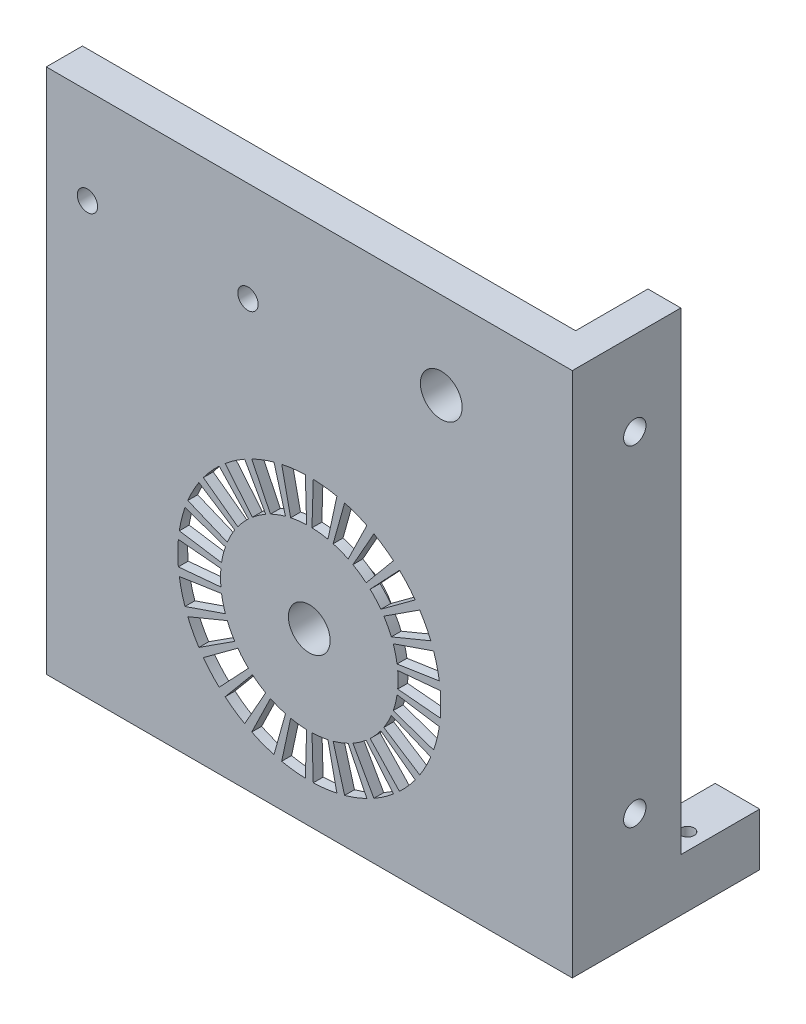
SolidWorks part; units mm, degrees
ref_plane "Front Plane" through (0, 0, 0) normal (0, 0, 1) x (1, 0, 0)
ref_plane "Top Plane" through (0, 0, 0) normal (0, 1, 0) x (1, 0, 0)
ref_plane "Right Plane" through (0, 0, 0) normal (1, 0, 0) x (0, 0, -1)
sketch "LED panel" plane through (0, 0, 0) normal (0, 0, 1) x (1, 0, 0)
  line L1 (-40, 40) -> (40, 40)
  line L2 (-40, 40) -> (-40, -40)
  line L3 (-40, -40) -> (40, -40)
  line L4 (40, 40) -> (40, -40)
  line L5 (-40, 40) -> (40, -40) construction
  line L6 (-40, -40) -> (40, 40) construction
  point P0 (0, 0)
  dimension "D1" = 80
  dimension "D2" = 80
extrude "Extrude LED panel" add sketch "LED panel" along normal blind 2.5
sketch "Sketch3" plane through (0, 0, 2.5) normal (0, 0, 1) x (1, 0, 0)
  circle A0 centre (0, -14) radius 5.9987
  circle A1 centre (20.0721, 26.7806) radius 6.0029
extrude "Boss-Extrude2" add sketch "Sketch3" against normal blind 7
sketch "Sketch1" plane through (0, 0, 2.5) normal (0, 0, 1) x (1, 0, 0)
  line L0 (-40, -14) -> (40, -14) construction
  line L3 (0, 40) -> (0, -40) construction
  line L4 (40, 40) -> (-40, 40) construction
  line L5 (-40, -40) -> (40, -40) construction
  line L6 (0, -14) -> (52.2337, -7.6577) construction
  line L7 (0, -14) -> (47.0949, -19.7184) construction
  line L8 (0, -14) -> (19.9179, -12.19) construction
  line L9 (0, -14) -> (41.9979, -17.8164) construction
  line L10 (13.4446, -12.7783) -> (19.9179, -12.19)
  line L11 (13.4446, -15.2217) -> (19.9179, -15.81)
  line L12 (13.3463, -16.0313) -> (19.7723, -17.0093)
  line L13 (12.7615, -18.4037) -> (18.906, -20.5241)
  line L14 (12.4724, -19.1662) -> (18.4776, -21.6537)
  line L15 (11.3368, -21.3298) -> (16.7953, -24.859)
  line L16 (10.8736, -22.0009) -> (16.109, -25.8532)
  line L17 (9.2533, -23.8299) -> (13.7085, -28.5628)
  line L18 (8.6429, -24.3707) -> (12.8043, -29.364)
  line L19 (6.6319, -25.7587) -> (9.8251, -31.4203)
  line L20 (5.9099, -26.1377) -> (8.7554, -31.9818)
  line L21 (3.6252, -27.0042) -> (5.3706, -33.2654)
  line L22 (2.8334, -27.1993) -> (4.1976, -33.5545)
  line L23 (0.4077, -27.4938) -> (0.6041, -33.9909)
  line L24 (-0.4077, -27.4938) -> (-0.6041, -33.9909)
  line L25 (-2.8334, -27.1993) -> (-4.1976, -33.5545)
  line L26 (-3.6252, -27.0042) -> (-5.3706, -33.2654)
  line L27 (-5.9099, -26.1377) -> (-8.7554, -31.9818)
  line L28 (-6.6319, -25.7587) -> (-9.8251, -31.4203)
  line L29 (-8.6429, -24.3707) -> (-12.8043, -29.364)
  line L30 (-9.2533, -23.8299) -> (-13.7085, -28.5628)
  line L31 (-10.8736, -22.0009) -> (-16.109, -25.8532)
  line L32 (-11.3368, -21.3298) -> (-16.7953, -24.859)
  line L33 (-12.4724, -19.1662) -> (-18.4776, -21.6537)
  line L34 (-12.7615, -18.4037) -> (-18.906, -20.5241)
  line L35 (-13.3463, -16.0313) -> (-19.7723, -17.0093)
  line L36 (-13.4446, -15.2217) -> (-19.9179, -15.81)
  line L37 (-13.4446, -12.7783) -> (-19.9179, -12.19)
  line L38 (-13.3463, -11.9687) -> (-19.7723, -10.9907)
  line L39 (-12.7615, -9.5963) -> (-18.906, -7.4759)
  line L40 (-12.4724, -8.8338) -> (-18.4776, -6.3463)
  line L41 (-11.3368, -6.6702) -> (-16.7953, -3.141)
  line L42 (-10.8736, -5.9991) -> (-16.109, -2.1468)
  line L43 (-9.2533, -4.1701) -> (-13.7085, 0.5628)
  line L44 (-8.6429, -3.6293) -> (-12.8043, 1.364)
  line L45 (-6.6319, -2.2413) -> (-9.8251, 3.4203)
  line L46 (-5.9099, -1.8623) -> (-8.7554, 3.9818)
  line L47 (-3.6252, -0.9958) -> (-5.3706, 5.2654)
  line L48 (-2.8334, -0.8007) -> (-4.1976, 5.5545)
  line L49 (-0.4077, -0.5062) -> (-0.6041, 5.9909)
  line L50 (0.4077, -0.5062) -> (0.6041, 5.9909)
  line L51 (2.8334, -0.8007) -> (4.1976, 5.5545)
  line L52 (3.6252, -0.9958) -> (5.3706, 5.2654)
  line L53 (5.9099, -1.8623) -> (8.7554, 3.9818)
  line L54 (6.6319, -2.2413) -> (9.8251, 3.4203)
  line L55 (8.6429, -3.6293) -> (12.8043, 1.364)
  line L56 (9.2533, -4.1701) -> (13.7085, 0.5628)
  line L57 (10.8736, -5.9991) -> (16.109, -2.1468)
  line L58 (11.3368, -6.6702) -> (16.7953, -3.141)
  line L59 (12.4724, -8.8338) -> (18.4776, -6.3463)
  line L60 (12.7615, -9.5963) -> (18.906, -7.4759)
  line L61 (13.3463, -11.9687) -> (19.7723, -10.9907)
  line L62 (-40, -40) -> (40, -40) construction
  line L63 (40, -40) -> (40, 40) construction
  line L64 (-40, 40) -> (-40, -40) construction
  arc A0 (19.9179, -15.81) -> (19.9179, -12.19) centre (0, -14) ccw
  arc A1 (13.4446, -15.2217) -> (13.4446, -12.7783) centre (0, -14) ccw
  arc A2 (18.906, -20.5241) -> (19.7723, -17.0093) centre (0, -14) ccw
  arc A3 (12.7615, -18.4037) -> (13.3463, -16.0313) centre (0, -14) ccw
  arc A4 (16.7953, -24.859) -> (18.4776, -21.6537) centre (0, -14) ccw
  arc A5 (11.3368, -21.3298) -> (12.4724, -19.1662) centre (0, -14) ccw
  arc A6 (13.7085, -28.5628) -> (16.109, -25.8532) centre (0, -14) ccw
  arc A7 (9.2533, -23.8299) -> (10.8736, -22.0009) centre (0, -14) ccw
  arc A8 (9.8251, -31.4203) -> (12.8043, -29.364) centre (0, -14) ccw
  arc A9 (6.6319, -25.7587) -> (8.6429, -24.3707) centre (0, -14) ccw
  arc A10 (5.3706, -33.2654) -> (8.7554, -31.9818) centre (0, -14) ccw
  arc A11 (3.6252, -27.0042) -> (5.9099, -26.1377) centre (0, -14) ccw
  arc A12 (0.6041, -33.9909) -> (4.1976, -33.5545) centre (0, -14) ccw
  arc A13 (0.4077, -27.4938) -> (2.8334, -27.1993) centre (0, -14) ccw
  arc A14 (-4.1976, -33.5545) -> (-0.6041, -33.9909) centre (0, -14) ccw
  arc A15 (-2.8334, -27.1993) -> (-0.4077, -27.4938) centre (0, -14) ccw
  arc A16 (-8.7554, -31.9818) -> (-5.3706, -33.2654) centre (0, -14) ccw
  arc A17 (-5.9099, -26.1377) -> (-3.6252, -27.0042) centre (0, -14) ccw
  arc A18 (-12.8043, -29.364) -> (-9.8251, -31.4203) centre (0, -14) ccw
  arc A19 (-8.6429, -24.3707) -> (-6.6319, -25.7587) centre (0, -14) ccw
  arc A20 (-16.109, -25.8532) -> (-13.7085, -28.5628) centre (0, -14) ccw
  arc A21 (-10.8736, -22.0009) -> (-9.2533, -23.8299) centre (0, -14) ccw
  arc A22 (-18.4776, -21.6537) -> (-16.7953, -24.859) centre (0, -14) ccw
  arc A23 (-12.4724, -19.1662) -> (-11.3368, -21.3298) centre (0, -14) ccw
  arc A24 (-19.7723, -17.0093) -> (-18.906, -20.5241) centre (0, -14) ccw
  arc A25 (-13.3463, -16.0313) -> (-12.7615, -18.4037) centre (0, -14) ccw
  arc A26 (-19.9179, -12.19) -> (-19.9179, -15.81) centre (0, -14) ccw
  arc A27 (-13.4446, -12.7783) -> (-13.4446, -15.2217) centre (0, -14) ccw
  arc A28 (-18.906, -7.4759) -> (-19.7723, -10.9907) centre (0, -14) ccw
  arc A29 (-12.7615, -9.5963) -> (-13.3463, -11.9687) centre (0, -14) ccw
  arc A30 (-16.7953, -3.141) -> (-18.4776, -6.3463) centre (0, -14) ccw
  arc A31 (-11.3368, -6.6702) -> (-12.4724, -8.8338) centre (0, -14) ccw
  arc A32 (-13.7085, 0.5628) -> (-16.109, -2.1468) centre (0, -14) ccw
  arc A33 (-9.2533, -4.1701) -> (-10.8736, -5.9991) centre (0, -14) ccw
  arc A34 (-9.8251, 3.4203) -> (-12.8043, 1.364) centre (0, -14) ccw
  arc A35 (-6.6319, -2.2413) -> (-8.6429, -3.6293) centre (0, -14) ccw
  arc A36 (-5.3706, 5.2654) -> (-8.7554, 3.9818) centre (0, -14) ccw
  arc A37 (-3.6252, -0.9958) -> (-5.9099, -1.8623) centre (0, -14) ccw
  arc A38 (-0.6041, 5.9909) -> (-4.1976, 5.5545) centre (0, -14) ccw
  arc A39 (-0.4077, -0.5062) -> (-2.8334, -0.8007) centre (0, -14) ccw
  arc A40 (4.1976, 5.5545) -> (0.6041, 5.9909) centre (0, -14) ccw
  arc A41 (2.8334, -0.8007) -> (0.4077, -0.5062) centre (0, -14) ccw
  arc A42 (8.7554, 3.9818) -> (5.3706, 5.2654) centre (0, -14) ccw
  arc A43 (5.9099, -1.8623) -> (3.6252, -0.9958) centre (0, -14) ccw
  arc A44 (12.8043, 1.364) -> (9.8251, 3.4203) centre (0, -14) ccw
  arc A45 (8.6429, -3.6293) -> (6.6319, -2.2413) centre (0, -14) ccw
  arc A46 (16.109, -2.1468) -> (13.7085, 0.5628) centre (0, -14) ccw
  arc A47 (10.8736, -5.9991) -> (9.2533, -4.1701) centre (0, -14) ccw
  arc A48 (18.4776, -6.3463) -> (16.7953, -3.141) centre (0, -14) ccw
  arc A49 (12.4724, -8.8338) -> (11.3368, -6.6702) centre (0, -14) ccw
  arc A50 (19.7723, -10.9907) -> (18.906, -7.4759) centre (0, -14) ccw
  arc A51 (13.3463, -11.9687) -> (12.7615, -9.5963) centre (0, -14) ccw
  circle A52 centre (0, -14) radius 3.175
  point P124 (0, -14)
  dimension "D2" = 40
  dimension "D4" = 6.5
  dimension "D9" = 6.35
  dimension "D1" = 6.923
  dimension "D3" = 6.923
  dimension "D5" = 5.192
  dimension "D6" = 5.192
  dimension "D8" = 26
  dimension "D7" = 26
extrude "Cut arrow indication holes" cut sketch "Sketch1" against normal through all
sketch "Sketch4" plane through (0, 0, 0) normal (0, 0, 1) x (1, 0, 0)
  circle A0 centre (20.0721, 26.7806) radius 3.175
  dimension "D1" = 6.35
  dimension "D2" = 20.0721
  dimension "D3" = 26.7806
extrude "Cut hole for secondary rod" cut sketch "Sketch4" along normal through all and the other way blind 7
sketch "Sketch2" plane through (0, 0, 0) normal (0, 0, -1) x (-1, 0, 0)
  line L0 (-1, 13.4818) -> (-1, 14.9818)
  line L1 (-1, 14.9818) -> (1, 14.9818)
  line L2 (1, 14.9818) -> (1, 13.4818)
  line L3 (0, -14) -> (0, 30.4199) construction
  line L4 (-8.9582, -40) -> (8.9582, -40)
  line L5 (40, -40) -> (-40, -40) construction
  arc A0 (-1, 13.4818) -> (-8.9582, -40) centre (0, -14) ccw
  arc A1 (8.9582, -40) -> (1, 13.4818) centre (0, -14) ccw
  circle A2 centre (0, -14) radius 5.9987
  point P5 (0, 14.9818)
  dimension "D1" = 55
  dimension "D2" = 2
  dimension "D3" = 1.5
extrude "Cut slot for PCB" cut sketch "Sketch2" against normal blind 1
sketch "Sketch6" plane through (0, 0, 0) normal (0, 0, -1) x (-1, 0, 0)
  line L0 (40, 40) -> (40, -40) construction
  line L1 (-40, 40) -> (40, 40)
  line L2 (-40, 40) -> (-40, 37)
  line L3 (-40, 37) -> (8.9219, 37)
  line L4 (40, 40) -> (40, -40)
  line L5 (37, 37) -> (37, -40)
  line L6 (8.9219, 37) -> (-40, 5.5647)
  line L7 (-40, -40) -> (-40, 40) construction
  line L8 (14.4714, 37) -> (-40, 1.9987)
  line L9 (40, -40) -> (8.9582, -40) construction
  line L10 (14.4714, 37) -> (37, 37)
  line L11 (-40, 5.5647) -> (-40, 1.9987)
  line L12 (40, -40) -> (37, -40)
  dimension "D1" = 3
  dimension "D2" = 3
  dimension "D3" = 3
extrude "Boss-Extrude3" add sketch "Sketch6" along normal blind 3
sketch "Sketch9" plane through (40, 0, 0) normal (1, 0, 0) x (0, 0, -1)
  line L0 (3, 40) -> (3, 37) construction
  line L1 (-2.5, 40) -> (14, 40)
  line L2 (-2.5, 40) -> (-2.5, -40)
  line L3 (-2.5, -40) -> (14, -40)
  line L4 (14, 40) -> (14, -40)
  dimension "D1" = 11
extrude "Boss-Extrude4" add sketch "Sketch9" against normal blind 5
sketch "Sketch11" plane through (0, 0, -14) normal (0, 0, -1) x (-1, 0, 0)
  line L0 (-35, -40) -> (-35, 40) construction
  line L1 (-40, -40) -> (-35, -40)
  line L2 (-40, -40) -> (-40, -32)
  line L3 (-40, -32) -> (-33.2309, -32)
  line L4 (-35, -40) -> (-33.2309, -32)
  dimension "D1" = 8
extrude "Boss-Extrude5" add sketch "Sketch11" along normal blind 12 and the other way up to surface (14 mm away) other way up to face at (-1.6792, -1.568, 0)
sketch "Sketch12" plane through (0, -32, 0) normal (0, 1, 0) x (1, 0, 0)
  line L0 (33.2309, 0) -> (35, 0) construction
  line L1 (40, 14) -> (40, 26) construction
  circle A0 centre (37.5, 17.53) radius 1
  dimension "D2" = 2.5
  dimension "D3" = 2
  dimension "D1" = 17.53
extrude "Cut-Extrude1" cut sketch "Sketch12" against normal through all
sketch "Sketch13" plane through (0, 0, 0) normal (0, 0, -1) x (-1, 0, 0)
  line L0 (40, 40) -> (-35, 40) construction
  line L1 (40, -40) -> (40, 40) construction
  circle A0 centre (33.74, 25.5) radius 3
  circle A1 centre (9.33, 24.81) radius 3
  dimension "D3" = 6
  dimension "D4" = 6
  dimension "D5" = 30.67
  dimension "D6" = 6.26
  dimension "D1" = 14.5
  dimension "D2" = 15.19
extrude "Boss-Extrude6" add sketch "Sketch13" along normal blind 3
sketch "Sketch14" plane through (0, 0, -3) normal (0, 0, -1) x (-1, 0, 0)
  circle A0 centre (33.74, 25.5) radius 1.55
  circle A1 centre (9.33, 24.81) radius 1.55
  dimension "D1" = 3.1
  dimension "D2" = 3.1
extrude "Cut-Extrude2" cut sketch "Sketch14" against normal through all
hole_wizard "CSK for M3 Flat Head Machine Screw1" positions "Sketch16" profile "Sketch15" countersink size "M3" standard "ANSI Metric" end condition through all
sketch "Sketch16" plane through (35, 0, 0) normal (-1, 0, 0) x (0, 0, 1)
  line L0 (-14, -32) -> (-14, 40) construction
  line L3 (0, 30.1119) -> (-14, 30.1119) construction
  line L4 (0, 8.7775) -> (0, 37) construction
  line L6 (-7, 30.1119) -> (-7, -44.9803) construction
  point P0 (-7, 27.1971)
  point P2 (-7, -23.0779)
sketch "Sketch15" plane through (35, 27.1971, -7) normal (0, 1, 0) x (0, 0, 1)
  line L0 (0, 0) -> (0, 5)
  line L1 (0, 5) -> (1.7, 5)
  line L2 (1.7, 5) -> (1.7, 1.45)
  line L3 (1.7, 1.45) -> (3.15, 0)
  line L5 (3.15, 0) -> (0, 0)
  line L6 (-1.7, 1.45) -> (-3.15, 0) construction
  line L11 (0, -6.35) -> (0, 107.95) construction
  dimension "Thru Hole Dia." = 3.4
  dimension "Thru Hole Depth" = 5
  dimension "Near C'Sink Dia." = 6.3
  dimension "Near C'Sink Angle" = 90
equation "\"D6@Sketch1\"=3/4*360/2/26"
